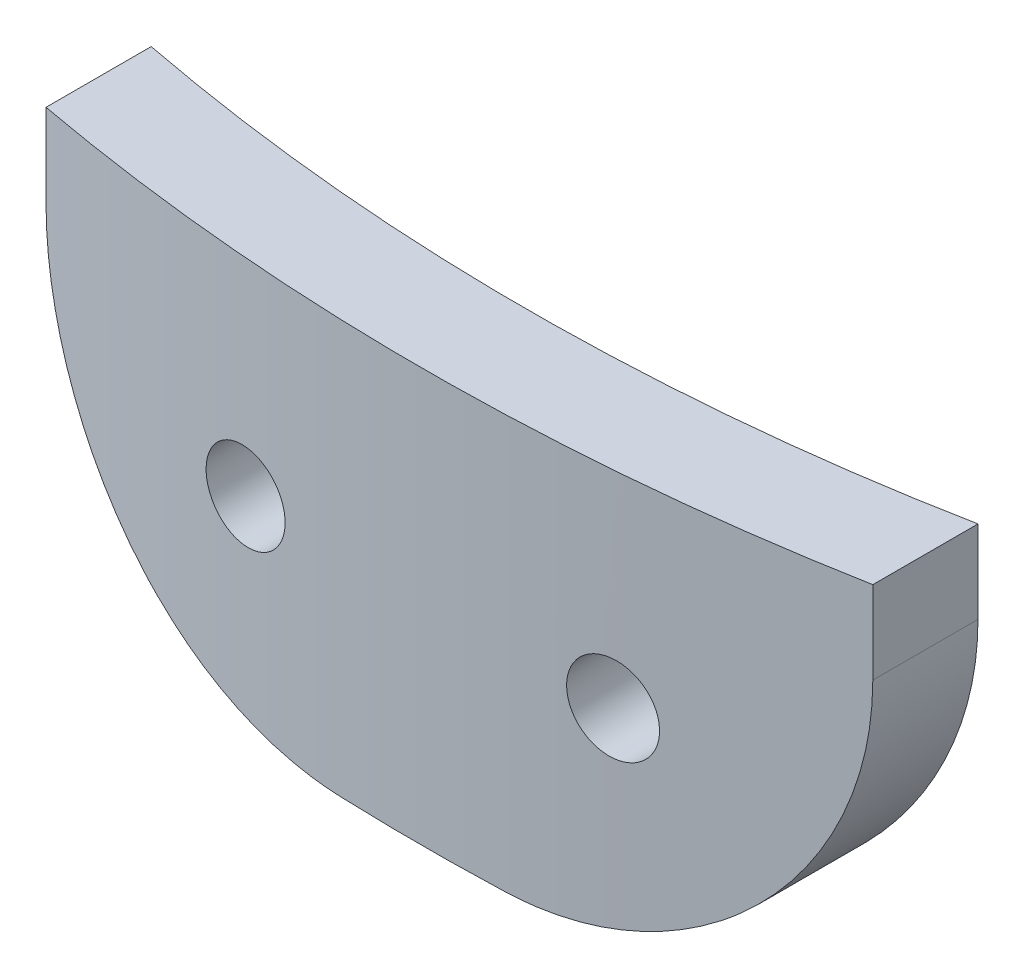
SolidWorks part; units mm, degrees
material "6061 Alloy"
ref_plane "Front Plane" through (0, 0, 0) normal (0, 0, 1) x (1, 0, 0)
ref_plane "Top Plane" through (0, 0, 0) normal (0, 1, 0) x (1, 0, 0)
ref_plane "Right Plane" through (0, 0, 0) normal (1, 0, 0) x (0, 0, -1)
sketch "Sketch1" plane through (0, 0, 0) normal (0, 1, 0) x (1, 0, 0)
  line L0 (-12.7, -65.4543) -> (-12.7, -68.6858)
  line L1 (12.7, -65.4543) -> (12.7, -68.6858)
  circle A0 centre (0, 0) radius 66.675
  circle A1 centre (0, 0) radius 69.85
  dimension "D1" = 133.35
  dimension "D3" = 12.7
  dimension "D4" = 12.7
  dimension "D2" = 3.175
extrude "Boss-Extrude1" add sketch "Sketch1" along normal blind 12.7 contours L0 A1 L1 A0 region at (0, 0, 67.8645)
sketch "Sketch2" plane through (0, 0, 0) normal (0, 0, 1) x (1, 0, 0)
  line L0 (0, 12.7) -> (0, 0) construction
  line L4 (-12.7, 0) -> (12.7, 0)
  line L5 (12.7, 0) -> (12.7, 12.7)
  line L6 (12.7, 12.7) -> (-12.7, 12.7)
  line L7 (-12.7, 12.7) -> (-12.7, 0)
  line L8 (-12.7, 0) -> (12.7, 0)
  line L9 (12.7, 0) -> (12.7, 12.7)
  line L10 (12.7, 12.7) -> (-12.7, 12.7)
  line L11 (-12.7, 12.7) -> (-12.7, 0)
  circle A0 centre (-5.6444, 6.35) radius 1.3208
  dimension "D3" = 12.7
  dimension "D6" = 2.6416
  dimension "D2" = 6.35
  dimension "D5" = 5.6444
extrude "Cut-Extrude1" cut sketch "Sketch2" along normal up to surface (69.7161 mm away) contours A0 up to face at (0, 6.35, 69.2679)
mirror "Mirror1" about plane through (0, 0, 0) normal (1, 0, 0) of "Cut-Extrude1"
sketch "Sketch3" plane through (0, 0, 0) normal (0, 0, 1) x (1, 0, 0)
  line L0 (-12.7, 12.7) -> (-12.7, 0)
  line L1 (-12.7, 0) -> (12.7, 0)
  line L2 (12.7, 0) -> (12.7, 12.7)
  line L4 (-12.7, 0) -> (12.7, 0)
  line L5 (12.7, 0) -> (12.7, 12.7)
  line L6 (12.7, 12.7) -> (-12.7, 12.7)
  line L7 (-12.7, 12.7) -> (-12.7, 0)
  line L8 (-2.54, 0) -> (2.54, 0)
  line L9 (12.7, 10.16) -> (12.7, 12.7)
  line L10 (12.7, 12.7) -> (-12.7, 12.7)
  line L11 (-12.7, 12.7) -> (-12.7, 10.16)
  arc A0 (2.54, 0) -> (12.7, 10.16) centre (2.54, 10.16) ccw
  arc A1 (-2.54, 0) -> (-12.7, 10.16) centre (-2.54, 10.16) cw
  dimension "D2" = 10.16
  dimension "D1" = 0
extrude "Cut-Extrude2" cut sketch "Sketch3" along normal up to surface (68.6858 mm away) contours L1 A1 L0 | A0 L1 L2 region at (-10.4306, 2.2694, 0) region at (10.4306, 2.2694, 0) up to face at (6.9299, 6.6537, 69.5054)
equation "\"Middle Coupler Inner Daimeter\"= 4.75in"
equation "\"Middle Coupler  Wall Thickness\" = 0.25in"
equation "\"Middle Coupler Bottom Thickness\"= 0.2in"
equation "\"Bearing Rail Offset\"= 0.45in"
equation "\"3-56 UNF Tap\"= 0.089in"
equation "\"3-56 UNF Clearance\"= 0.104in"
equation "\"Ball Bearing Distance\"= 0.03in"
equation "\"TCA Outer Diameter\" = 6.625in"
equation "\"D1@Sketch1\"=\"Middle Coupler Inner Daimeter\"+0.5"
equation "\"D2@Sketch1\"=1/8"
equation "\"D3@Sketch1\"=0.5"
equation "\"D4@Sketch1\"=\"D3@Sketch1\""
equation "\"D2@Sketch2\"=\"D3@Sketch2\"/2"
equation "\"D6@Sketch2\"=\"3-56 UNF Clearance\""
equation "\"D5@Sketch2\"=\"D4@Sketch2\"/4.5"
equation "\"Interstage Aeroframe Wall Thickness\" = 0.072in"
equation "\"Compression Spring OD\"= 0.42in"
equation "\"10-24 Tap\"= 0.157in"
equation "\"10-24 Clearance\"= 0.196in"
equation "\"Lower Stage Fuselage Wall Thickness\" = 0.25in"
equation "\"6-32 Tap\" = 0.107in"
equation "\"1/4-20 Tap\" = 0.201in"
